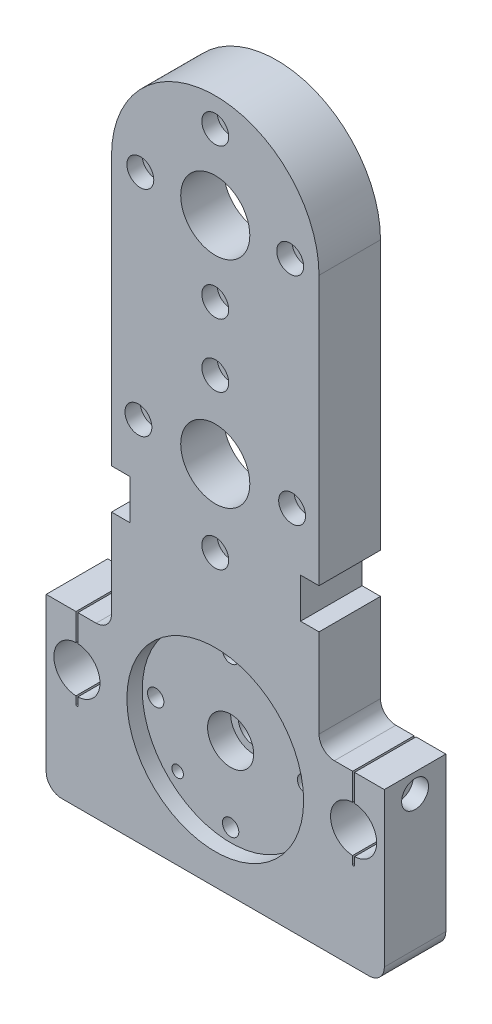
SolidWorks part; units mm, degrees
material "6061 Alloy"
ref_plane "Front" through (0, 0, 0) normal (0, 0, 1) x (1, 0, 0)
ref_plane "Top" through (0, 0, 0) normal (0, 1, 0) x (1, 0, 0)
ref_plane "Right" through (0, 0, 0) normal (1, 0, 0) x (0, 0, -1)
ref_axis "Axis" through (0, 0, -80.9) along (0, 0, 1)
sketch "Bolt circle" plane through (0, 0, 0) normal (0, 0, 1) x (1, 0, 0)
  line L0 (0, 36.5125) -> (0, 25.4) construction
  line L1 (-42.8625, 88.9) -> (-42.8625, -22.1615)
  line L2 (0, 114.3) -> (0, 125.4125) construction
  line L3 (42.8625, 88.9) -> (42.8625, -22.1615)
  line L4 (42.8625, -38.6715) -> (42.8625, -81.5975)
  line L5 (42.8625, -38.6715) -> (35.2425, -38.6715)
  line L6 (-42.8625, -22.1615) -> (-35.2425, -22.1615)
  line L7 (42.8625, -81.5975) -> (69.85, -81.5975)
  line L8 (42.8625, -22.1615) -> (35.2425, -22.1615)
  line L9 (35.2425, -38.6715) -> (35.2425, -22.1615)
  line L10 (-42.8625, -38.6715) -> (-35.2425, -38.6715)
  line L11 (-35.2425, -38.6715) -> (-35.2425, -22.1615)
  line L12 (-42.8625, -81.5975) -> (-69.85, -81.5975)
  line L13 (-42.8625, -38.6715) -> (-42.8625, -81.5975)
  line L30 (69.85, -81.5975) -> (69.85, -151.4475)
  line L31 (69.85, -151.4475) -> (-69.85, -151.4475)
  line L34 (-69.85, -81.5975) -> (-69.85, -151.4475)
  line L35 (0, 0) -> (0, -151.4475) construction
  circle A0 centre (0, 0) radius 36.5125 construction
  circle A1 centre (0, 0) radius 25.4 construction
  circle A2 centre (0, 0) radius 30.9562 construction
  arc A3 (-42.8625, 88.9) -> (42.8625, 88.9) centre (0, 88.9) cw
  circle A4 centre (0, 88.9) radius 14.2748
  circle A5 centre (0, 88.9) radius 36.5125 construction
  circle A6 centre (0, 88.9) radius 25.4 construction
  circle A7 centre (0, 0) radius 14.2748
  circle A8 centre (0, -102.235) radius 36.5125 construction
  circle A9 centre (0, -102.235) radius 6.35
  circle A10 centre (0, 88.9) radius 30.9562 construction
  point P0 (0, -36.5125)
  point P7 (0, 30.9562)
  point P9 (0, -138.7475)
  point P20 (0, 119.8562)
  point P28 (39.0525, -38.6715)
  dimension "D1" = 73.025
  dimension "D2" = 50.8
  dimension "D3" = 69.85
  dimension "D12" = 139.7
  dimension "D5" = 26.9875
  dimension "D11" = 49.2125
  dimension "D13" = 28.5496
  dimension "D18" = 12.7
  dimension "D15" = 16.51
  dimension "D6" = 88.9
  dimension "D8" = 73.025
  dimension "D9" = 28.5496
  dimension "D10" = 50.8
  dimension "D4" = 102.235
  dimension "D7" = 85.725
  dimension "D14" = 42.926
  dimension "D16" = 7.62
  dimension "D17" = 12.7
extrude "Base" add sketch "Bolt circle" along normal mid plane 25.4
hole_wizard "Structure tube connection counterbore" positions "Sketch15" profile "Sketch14" counterbore size "1/4" standard "Ansi Inch" end condition through all
sketch "Sketch15" plane through (0, 0, -12.7) normal (0, 0, -1) x (-1, 0, 0)
  circle A0 centre (0, -102.235) radius 30.9563 construction
  point P1 (0, -71.2788)
  dimension "D1" = 61.9125
sketch "Sketch14" plane through (0, -71.2788, -12.7) normal (1, 0, 0) x (0, 1, 0)
  line L0 (0, 0) -> (0, 25.4)
  line L1 (0, 25.4) -> (3.3782, 25.4)
  line L3 (3.3782, 25.4) -> (3.3782, 6.35)
  line L4 (3.3782, 6.35) -> (5.5562, 6.35)
  line L5 (5.5562, 6.35) -> (5.5562, 0)
  line L7 (5.5562, 0) -> (0, 0)
  line L11 (0, -6.35) -> (0, 107.95) construction
  dimension "Thru Hole Dia." = 6.7564
  dimension "Thru Hole Depth" = 25.4
  dimension "C'Bore Dia." = 11.1125
  dimension "C'Bore Depth" = 6.35
pattern_circular "Structure tube connection counterbore pattern" count 4 over 360 about axis through (0, -102.235, 12.7) along (0, 0, -1) of "Structure tube connection counterbore"
hole_wizard "Spindle connection counterbore" positions "Sketch11" profile "Sketch10" counterbore size "1/4" standard "Ansi Inch" end condition through all
sketch "Sketch11" plane through (0, 0, 12.7) normal (0, 0, 1) x (1, 0, 0)
  circle A0 centre (0, 0) radius 31.75 construction
  point P0 (0, 31.75)
  dimension "D1" = 63.5
sketch "Sketch10" plane through (0, 31.75, 12.7) normal (1, 0, 0) x (0, -1, 0)
  line L0 (0, 0) -> (0, 25.4)
  line L1 (0, 25.4) -> (3.3782, 25.4)
  line L3 (3.3782, 25.4) -> (3.3782, 6.35)
  line L4 (3.3782, 6.35) -> (5.5562, 6.35)
  line L5 (5.5562, 6.35) -> (5.5562, 0)
  line L7 (5.5562, 0) -> (0, 0)
  line L11 (0, -6.35) -> (0, 107.95) construction
  dimension "Thru Hole Dia." = 6.7564
  dimension "Thru Hole Depth" = 25.4
  dimension "C'Bore Dia." = 11.1125
  dimension "C'Bore Depth" = 6.35
pattern_circular "Spindle connection counterbore pattern" count 4 over 360 about axis through (0, 0, 12.7) along (0, 0, -1) of "Spindle connection counterbore"
sketch "Sketch16" plane through (0, 0, 12.7) normal (0, 0, 1) x (1, 0, 0)
  circle A0 centre (0, -102.235) radius 36.5125
  dimension "D1" = 73.025
extrude "Structure tube mounting pocket" cut sketch "Sketch16" against normal blind 6.35
sketch "Sketch17" plane through (0, 0, -12.7) normal (0, 0, -1) x (-1, 0, 0)
  circle A0 centre (0, 0) radius 36.5125
  circle A1 centre (0, -102.235) radius 36.5125 construction
  dimension "D1" = 73.025
extrude "Spindle mounting pocket" cut sketch "Sketch17" against normal blind 7.62
sketch "Sketch18" plane through (0, 0, 6.35) normal (0, 0, 1) x (1, 0, 0)
  circle A0 centre (0, -102.235) radius 9.525
  dimension "D1" = 19.05
extrude "Lead screw through hole" cut sketch "Sketch18" against normal blind 9.525
sketch "Sketch20" plane through (0, 0, 12.7) normal (0, 0, 1) x (1, 0, 0)
  line L1 (57.15, -102.235) -> (-57.15, -102.235) construction
  circle A0 centre (57.15, -102.235) radius 9.525
  circle A1 centre (-57.15, -102.235) radius 9.525
  dimension "D2" = 114.3
  dimension "D3" = 19.05
extrude "Rail mounting pilot_holes" cut sketch "Sketch20" against normal through all
sketch "Sketch27" plane through (0, 0, 6.35) normal (0, 0, 1) x (1, 0, 0)
  line L0 (20.6813, -78.1454) -> (19.6028, -79.3103)
  line L1 (24.176, -81.381) -> (23.0974, -82.5459)
  line L2 (21.8894, -80.3456) -> (-21.8894, -124.1244) construction
  line L3 (20.1421, -78.7278) -> (23.6367, -81.9634) construction
  line L4 (50, 0) -> (-50, 0) construction
  circle A0 centre (-21.8894, -124.1244) radius 2.3813
  arc A1 (24.176, -81.381) -> (20.6813, -78.1454) centre (22.4286, -79.7632) ccw
  arc A2 (23.0974, -82.5459) -> (19.6028, -79.3103) centre (21.3501, -80.9281) cw
  circle A3 centre (21.8894, -80.3456) radius 2.3813 construction
  circle A4 centre (0, -102.235) radius 30.9563 construction
  point P10 (20.1421, -78.7278)
  dimension "D2" = 45
  dimension "D3" = 4.7625
  dimension "D1" = 1.5875
extrude "Alignment_features" cut sketch "Sketch27" against normal blind 6.35
fillet "Generic_rounding_fillet" radius 6.35 4 edges at (-69.85, -151.4475, 0) (69.85, -151.4475, 0) (-42.8625, -81.5975, 0) (42.8625, -81.5975, 0)
sketch "Sketch21" plane through (0, -151.4475, 0) normal (0, -1, 0) x (1, 0, 0)
  line L0 (69.85, 0) -> (-69.85, 0) construction
  line L1 (69.85, 12.7) -> (69.85, -12.7) construction
  line L2 (-69.85, 12.7) -> (-69.85, -12.7) construction
  line L3 (0, -12.7) -> (0, 12.7) construction
  line L4 (-63.5, -12.7) -> (63.5, -12.7) construction
  line L5 (-63.5, 12.7) -> (63.5, 12.7) construction
  circle A0 centre (57.15, 0) radius 4.7625
  circle A1 centre (-57.15, 0) radius 4.7625
  dimension "D1" = 9.525
  dimension "D2" = 114.3
extrude "Point_mount_bores" [suppressed] cut sketch "Sketch21" against normal blind 6.35
sketch "Sketch22" plane through (0, 0, 12.7) normal (0, 0, 1) x (1, 0, 0)
  line L0 (69.85, -81.5975) -> (49.2125, -81.5975) construction
  line L1 (56.7531, -81.5975) -> (57.5469, -81.5975)
  line L2 (56.7531, -81.5975) -> (56.7531, -114.935)
  line L3 (57.15, -114.935) -> (57.15, -102.235) construction
  line L4 (57.5469, -81.5975) -> (57.5469, -114.935)
  line L5 (0, -151.4475) -> (0, 131.7625) construction
  line L6 (-63.5, -151.4475) -> (63.5, -151.4475) construction
  line L7 (-57.15, -114.935) -> (-57.15, -102.235) construction
  line L8 (-57.5469, -81.5975) -> (-57.5469, -114.935)
  line L9 (-56.7531, -81.5975) -> (-56.7531, -114.935)
  line L10 (-56.7531, -81.5975) -> (-57.5469, -81.5975)
  arc A0 (56.7531, -114.935) -> (57.5469, -114.935) centre (57.15, -114.935) ccw
  arc A2 (-56.7531, -114.935) -> (-57.5469, -114.935) centre (-57.15, -114.935) cw
  arc A3 (42.8625, 88.9) -> (-42.8625, 88.9) centre (0, 88.9) ccw construction
  dimension "D1" = 0.7937
  dimension "D2" = 12.7
extrude "Flexure_clamp_slits" cut sketch "Sketch22" against normal through all
hole_wizard "Flexure_clamp_counterbore" positions "Sketch24" profile "Sketch23" counterbore size "1/4" standard "Ansi Inch" end condition up to next
sketch "Sketch24" plane through (69.85, 0, 0) normal (1, 0, 0) x (0, 0, -1)
  line L0 (0, 50) -> (0, -50) construction
  line L1 (-12.7, -81.5975) -> (12.7, -81.5975) construction
  point P0 (0, -89.535)
  dimension "D1" = 7.9375
sketch "Sketch23" plane through (69.85, -89.535, 0) normal (0, 1, 0) x (0, 0, -1)
  line L0 (0, 0) -> (0, 12.3031)
  line L1 (0, 12.3031) -> (3.3782, 12.3031)
  line L3 (3.3782, 12.3031) -> (3.3782, 6.35)
  line L4 (3.3782, 6.35) -> (5.5562, 6.35)
  line L5 (5.5562, 6.35) -> (5.5562, 0)
  line L7 (5.5562, 0) -> (0, 0)
  line L11 (0, -6.35) -> (0, 107.95) construction
  dimension "Thru Hole Dia." = 6.7564
  dimension "Thru Hole Depth" = 12.3031
  dimension "C'Bore Dia." = 11.1125
  dimension "C'Bore Depth" = 6.35
hole_wizard "Flexure_clamp_threads" positions "Sketch26" profile "Sketch25" tap size "1/4-20" standard "Ansi Inch"
sketch "Sketch26" plane through (56.7531, 0, 0) normal (1, 0, 0) x (0, 0, -1)
  point P1 (0, -89.535)
sketch "Sketch25" plane through (56.7531, -89.535, 0) normal (0, 1, 0) x (0, 0, -1)
  line L0 (0, 0) -> (0, 18.0438)
  line L1 (0, 18.0438) -> (2.5527, 16.51)
  line L2 (2.5527, 16.51) -> (2.5527, 0)
  line L5 (2.5527, 0) -> (0, 0)
  line L10 (0, 18.0438) -> (-2.5527, 16.51) construction
  line L11 (0, -6.35) -> (0, 107.95) construction
  dimension "Tap Drill Dia." = 5.1054
  dimension "Tap Drill Depth" = 16.51
  dimension "Drill Angle" = 118
cosmetic thread "Hole Thread2" parameters "D1"=12.7, "D2"=6.35
mirror "Flexure_clamp_fastener_holes" about plane through (0, 0, 0) normal (1, 0, 0) of "Flexure_clamp_counterbore", "Flexure_clamp_threads"
hole_wizard "wood_spindle_CBORE" positions "Sketch28" profile "Sketch29" counterbore size "1/4" standard "ANSI Inch" end condition through all
sketch "Sketch28" plane through (0, 0, 12.7) normal (0, 0, 1) x (1, 0, 0)
  point P0 (0, 119.8562)
sketch "Sketch29" plane through (0, 119.8562, 12.7) normal (1, 0, 0) x (0, -1, 0)
  line L0 (0, 0) -> (0, 25.4)
  line L1 (0, 25.4) -> (3.3782, 25.4)
  line L3 (3.3782, 25.4) -> (3.3782, 6.35)
  line L4 (3.3782, 6.35) -> (5.5562, 6.35)
  line L5 (5.5562, 6.35) -> (5.5562, 0)
  line L7 (5.5562, 0) -> (0, 0)
  line L11 (0, -6.35) -> (0, 107.95) construction
  dimension "Thru Hole Dia." = 6.7564
  dimension "Thru Hole Depth" = 25.4
  dimension "C'Bore Dia." = 11.1125
  dimension "C'Bore Depth" = 6.35
pattern_circular "CirPattern1" count 4 over 360 about axis through (0, 88.9, 12.7) along (0, 0, -1) of "wood_spindle_CBORE"
sketch "Sketch30" plane through (0, 0, -12.7) normal (0, 0, -1) x (-1, 0, 0)
  circle A0 centre (0, 88.9) radius 36.5125
  dimension "D1" = 73.025
extrude "Cut-Extrude1" cut sketch "Sketch30" against normal blind 7.62
